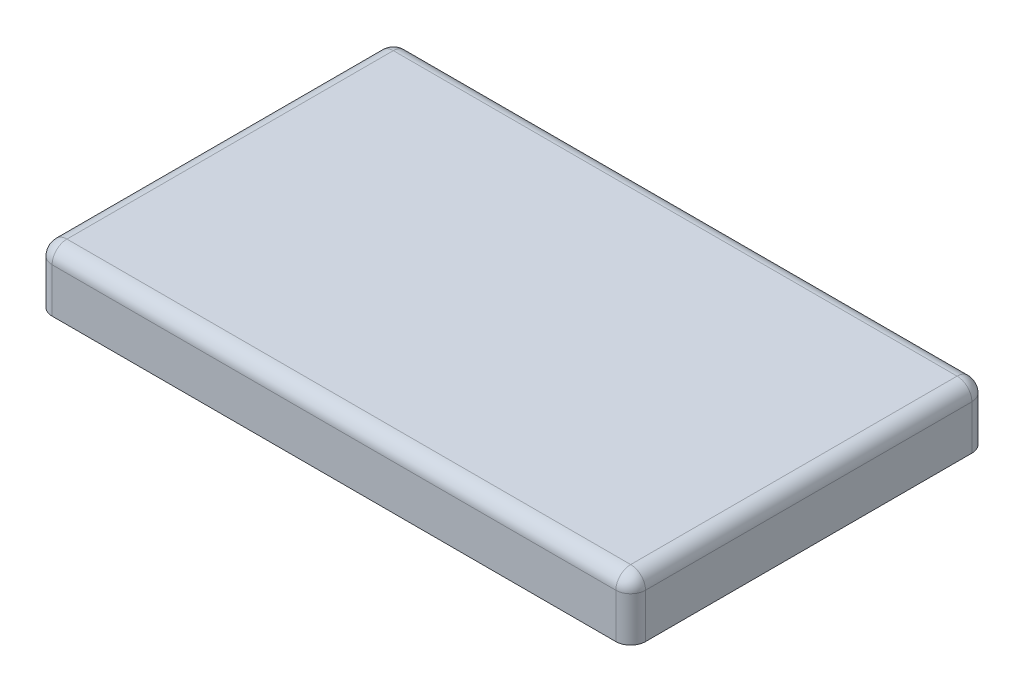
SolidWorks part; units mm, degrees
material "Acrylic (Medium-high impact)"
ref_plane "Front Plane" through (0, 0, 0) normal (0, 0, 1) x (1, 0, 0)
ref_plane "Top Plane" through (0, 0, 0) normal (0, 1, 0) x (1, 0, 0)
ref_plane "Right Plane" through (0, 0, 0) normal (1, 0, 0) x (0, 0, -1)
sketch "Sketch1" plane through (0, 0, 0) normal (0, 1, 0) x (1, 0, 0)
  line L1 (-47.5, -30) -> (47.5, -30)
  line L2 (-50, -27.5) -> (-50, 27.5)
  line L3 (-47.5, 30) -> (47.5, 30)
  line L4 (50, -27.5) -> (50, 27.5)
  line L5 (-50, -30) -> (50, 30) construction
  line L6 (-50, 30) -> (50, -30) construction
  arc A0 (-47.5, -30) -> (-50, -27.5) centre (-47.5, -27.5) cw
  arc A1 (47.5, -30) -> (50, -27.5) centre (47.5, -27.5) ccw
  arc A2 (47.5, 30) -> (50, 27.5) centre (47.5, 27.5) cw
  arc A3 (-50, 27.5) -> (-47.5, 30) centre (-47.5, 27.5) cw
  point P0 (0, 0)
  dimension "D3" = 2.5
  dimension "D1" = 100
  dimension "D2" = 60
extrude "Boss-Extrude1" add sketch "Sketch1" along normal blind 10
shell "Shell1" thickness 1.25 removed face at (0, 0, 0)
fillet "Fillet1" radius 2.5 8 edges at (-50, 10, 0) (-49.2678, 10, -29.2678) (0, 10, -30) (49.2678, 10, -29.2678) (50, 10, 0) (49.2678, 10, 29.2678) (0, 10, 30) (-49.2678, 10, 29.2678)
chamfer "Chamfer1" distance 1.25 angle 45 8 edges at (-48.75, 0, 0) (-48.3839, 0, -28.3839) (-48.3839, 0, 28.3839) (0, 0, -28.75) (0, 0, 28.75) (48.3839, 0, -28.3839) (48.75, 0, 0) (48.3839, 0, 28.3839)
